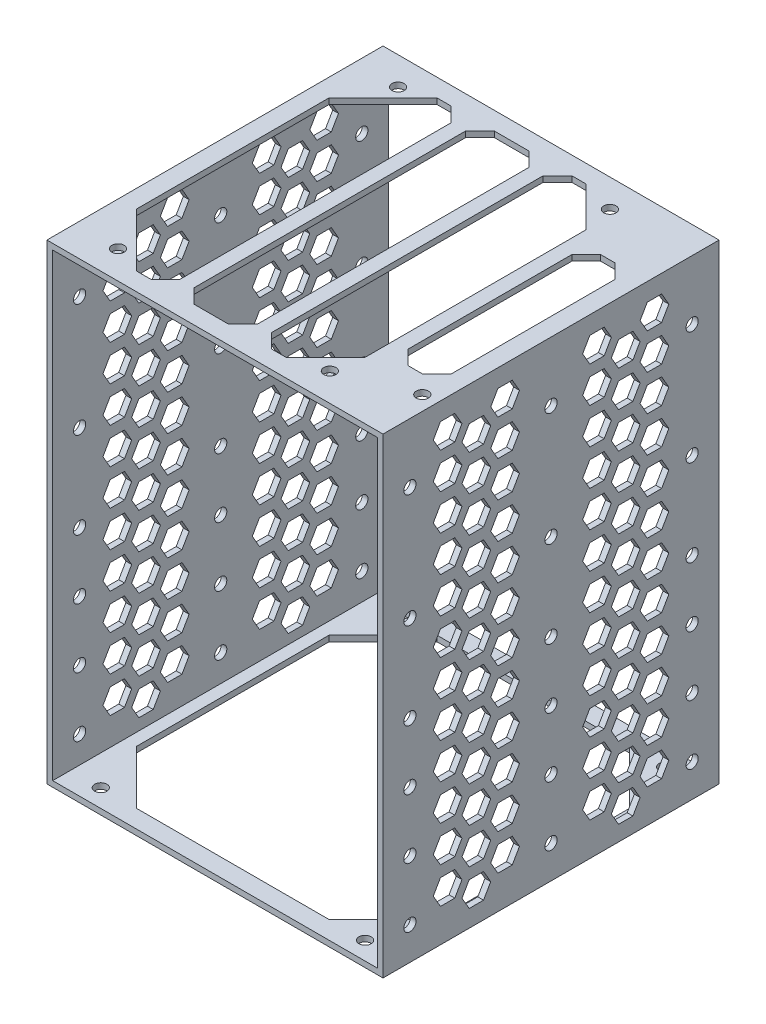
SolidWorks part; units mm, degrees
ref_plane "Front Plane" through (0, 0, 0) normal (0, 0, 1) x (1, 0, 0)
ref_plane "Top Plane" through (0, 0, 0) normal (0, 1, 0) x (1, 0, 0)
ref_plane "Right Plane" through (0, 0, 0) normal (1, 0, 0) x (0, 0, -1)
sketch "Sketch1" plane through (0, 0, 0) normal (0, 0, 1) x (1, 0, 0)
  line L0 (-45.2, 26.84) -> (45.2, 26.84)
  line L1 (45.2, 26.84) -> (45.2, -101.16)
  line L2 (45.2, -101.16) -> (-45.2, -101.16)
  line L3 (-45.2, -101.16) -> (-45.2, 26.84)
  line L5 (-46.8, 28.44) -> (46.8, 28.44)
  line L6 (-46.8, 28.44) -> (-46.8, -102.76)
  line L7 (-46.8, -102.76) -> (46.8, -102.76)
  line L8 (46.8, 28.44) -> (46.8, -102.76)
  dimension "D1" = 90.4
  dimension "D2" = 128
  dimension "D3" = 1.6
  dimension "D4" = 1.6
  dimension "D5" = 1.6
  dimension "D6" = 1.6
  dimension "D7" = 45.2
  dimension "D8" = 45.2
extrude "Boss-Extrude1" add sketch "Sketch1" along normal blind 93.6
sketch "Sketch2" plane through (46.8, 0, 0) normal (1, 0, 0) x (0, 0, -1)
  line L0 (-93.6, 28.44) -> (-93.6, -102.76)
  line L1 (-93.6, 28.44) -> (0, 28.44) construction
  line L2 (-93.6, -102.76) -> (-93.6, 28.44) construction
  line L3 (-93.6, -102.76) -> (0, -102.76) construction
  line L4 (-93.6, -85.36) -> (0, -85.36) construction
  line L5 (0, -102.76) -> (0, 28.44) construction
  line L6 (-93.6, -68.76) -> (0, -68.76) construction
  line L7 (-93.6, -52.16) -> (0, -52.16) construction
  line L8 (-93.6, -35.56) -> (0, -35.56) construction
  line L9 (-93.6, -3.96) -> (0, -3.96) construction
  line L10 (-93.6, -43.86) -> (0, -43.86)
  line L11 (-93.6, -60.46) -> (0, -60.46)
  line L12 (-93.6, -77.06) -> (0, -77.06)
  line L13 (-93.6, -93.66) -> (0, -93.66)
  line L14 (-93.6, -19.76) -> (0, -19.76)
  line L15 (-93.6, 11.84) -> (0, 11.84)
  line L16 (-93.6, -12.26) -> (0, -12.26)
  line L17 (-93.6, -84.56) -> (0, -84.56)
  line L18 (0, -84.56) -> (0, -86.16)
  line L19 (0, -86.16) -> (-93.6, -86.16)
  line L20 (-93.6, -67.96) -> (0, -67.96)
  line L21 (0, -67.96) -> (0, -69.56)
  line L22 (0, -69.56) -> (-93.6, -69.56)
  line L23 (-93.6, -51.36) -> (0, -51.36)
  line L24 (0, -51.36) -> (0, -52.96)
  line L25 (0, -52.96) -> (-93.6, -52.96)
  line L26 (-93.6, -34.76) -> (0, -34.76)
  line L27 (-93.6, -36.36) -> (0, -36.36)
  line L29 (-93.6, -3.16) -> (0, -3.16)
  line L30 (0, -3.16) -> (0, -4.76)
  line L31 (0, -4.76) -> (-93.6, -4.76)
  circle A11 centre (-86.1, 11.84) radius 0.75
  circle A13 centre (-86.1, -19.76) radius 0.75
  circle A14 centre (-86.1, -43.86) radius 0.75
  circle A15 centre (-86.1, -60.46) radius 0.75
  circle A16 centre (-86.1, -77.06) radius 0.75
  circle A17 centre (-86.1, -93.66) radius 0.75
  circle A18 centre (-7.5, 11.84) radius 0.75
  circle A20 centre (-7.5, -19.76) radius 0.75
  circle A21 centre (-7.5, -43.86) radius 0.75
  circle A22 centre (-7.5, -60.46) radius 0.75
  circle A23 centre (-7.5, -77.06) radius 0.75
  circle A24 centre (-7.5, -93.66) radius 0.75
  circle A27 centre (-46.8, 11.84) radius 0.75
  circle A29 centre (-46.8, -19.76) radius 0.75
  circle A30 centre (-46.8, -43.86) radius 0.75
  circle A31 centre (-46.8, -60.46) radius 0.75
  circle A32 centre (-46.8, -77.06) radius 0.75
  circle A33 centre (-46.8, -93.66) radius 0.75
  dimension "D7" = 16.6
  dimension "D8" = 15.8
  dimension "D9" = 8.3
  dimension "D10" = 8.3
  dimension "D11" = 8.3
  dimension "D12" = 8.3
  dimension "D13" = 1.5
  dimension "D14" = 7.5
  dimension "D15" = 7.5
  dimension "D16" = 1.5
  dimension "D17" = 1.5
  dimension "D18" = 1.5
  dimension "D19" = 1.5
  dimension "D20" = 1.5
  dimension "D21" = 1.5
  dimension "D22" = 1.5
  dimension "D23" = 1.5
  dimension "D24" = 1.5
  dimension "D25" = 1.5
  dimension "D26" = 1.5
  dimension "D39" = 1.5
  dimension "D1" = 17.4
  dimension "D2" = 16.6
  dimension "D3" = 16.6
  dimension "D4" = 16.6
  dimension "D5" = 31.6
  dimension "D6" = 32.4
  dimension "D27" = 8.3
  dimension "D28" = 0.8
  dimension "D29" = 0.8
  dimension "D30" = 0.8
  dimension "D31" = 0.8
  dimension "D32" = 0.8
  dimension "D33" = 0.8
  dimension "D34" = 0.8
  dimension "D35" = 0.8
  dimension "D36" = 0.8
  dimension "D37" = 0.8
  dimension "D38" = 15
extrude "Cut-Extrude1" cut sketch "Sketch2" against normal blind 100 contours L15 A11 | L15 A11 | L15 A18 | L15 A18 | L14 A13 | L14 A13 | L10 A21 | L10 A14 | L11 A15 | L11 A22 | L11 A22 | L12 A16 | L12 A16 | L12 A23 | L13 A17 | L13 A17 | L12 A23 | L13 A24 | L13 A24 | A20 | A21 | A14 | A15 | A27 | A29 | A30 | A31 | A32 | A33 region at (46.8, -19.4417, 86.1) region at (46.8, -20.0783, 86.1) region at (46.8, -44.1783, 7.5) region at (46.8, -43.5417, 86.1) region at (46.8, -60.1417, 7.5) region at (46.8, -60.7783, 7.5) region at (46.8, -60.1417, 86.1) region at (46.8, -76.7417, 7.5) region at (46.8, -77.3783, 7.5) region at (46.8, -76.7417, 86.1) region at (46.8, -77.3783, 86.1) region at (46.8, -93.3417, 7.5) region at (46.8, -93.9783, 7.5) region at (46.8, -93.3417, 86.1) region at (46.8, -93.9783, 86.1) region at (46.8, 12.1583, 7.5) region at (46.8, 11.5217, 7.5) region at (46.8, 12.1583, 86.1) region at (46.8, 11.5217, 86.1)
sketch "Sketch6" plane through (46.8, 0, 0) normal (1, 0, 0) x (0, 0, -1)
  line L18 (-93.6, 28.44) -> (0, 28.44) construction
  line L26 (-79.6, 19.9759) -> (-77.6, 23.44)
  line L27 (-77.6, 23.44) -> (-73.6, 23.44)
  line L28 (-73.6, 23.44) -> (-71.6, 19.9759)
  line L29 (-71.6, 19.9759) -> (-73.6, 16.5118)
  line L30 (-73.6, 16.5118) -> (-77.6, 16.5118)
  line L31 (-77.6, 16.5118) -> (-79.6, 19.9759)
  line L32 (-71.6, 15.4759) -> (-69.6, 18.94)
  line L33 (-69.6, 18.94) -> (-65.6, 18.94)
  line L34 (-65.6, 18.94) -> (-63.6, 15.4759)
  line L35 (-63.6, 15.4759) -> (-65.6, 12.0118)
  line L36 (-65.6, 12.0118) -> (-69.6, 12.0118)
  line L37 (-69.6, 12.0118) -> (-71.6, 15.4759)
  line L38 (-63.6, 19.9759) -> (-61.6, 23.44)
  line L39 (-61.6, 23.44) -> (-57.6, 23.44)
  line L40 (-57.6, 23.44) -> (-55.6, 19.9759)
  line L41 (-55.6, 19.9759) -> (-57.6, 16.5118)
  line L42 (-57.6, 16.5118) -> (-61.6, 16.5118)
  line L43 (-61.6, 16.5118) -> (-63.6, 19.9759)
  line L44 (-38, 19.9759) -> (-36, 23.44)
  line L45 (-36, 23.44) -> (-32, 23.44)
  line L46 (-32, 23.44) -> (-30, 19.9759)
  line L47 (-30, 19.9759) -> (-32, 16.5118)
  line L48 (-32, 16.5118) -> (-36, 16.5118)
  line L49 (-36, 16.5118) -> (-38, 19.9759)
  line L50 (-30, 14.9759) -> (-28, 18.44)
  line L51 (-28, 18.44) -> (-24, 18.44)
  line L52 (-24, 18.44) -> (-22, 14.9759)
  line L53 (-22, 14.9759) -> (-24, 11.5118)
  line L54 (-24, 11.5118) -> (-28, 11.5118)
  line L55 (-28, 11.5118) -> (-30, 14.9759)
  line L56 (-22, 19.9759) -> (-20, 23.44)
  line L57 (-20, 23.44) -> (-16, 23.44)
  line L58 (-16, 23.44) -> (-14, 19.9759)
  line L59 (-14, 19.9759) -> (-16, 16.5118)
  line L60 (-16, 16.5118) -> (-20, 16.5118)
  line L61 (-20, 16.5118) -> (-22, 19.9759)
  circle A0 centre (-86.1, 11.84) radius 0.75 construction
  circle A1 centre (-7.5, 11.84) radius 0.75 construction
  dimension "D1" = 120
  dimension "D2" = 120
  dimension "D3" = 120
  dimension "D4" = 4
  dimension "D5" = 4
  dimension "D6" = 4
  dimension "D7" = 120
  dimension "D8" = 120
  dimension "D9" = 120
  dimension "D10" = 4
  dimension "D11" = 4
  dimension "D12" = 4
  dimension "D13" = 2.25
  dimension "D14" = 120
  dimension "D15" = 120
  dimension "D16" = 120
  dimension "D17" = 4
  dimension "D18" = 4
  dimension "D19" = 4
  dimension "D20" = 4
  dimension "D21" = 4
  dimension "D22" = 4
  dimension "D23" = 120
  dimension "D24" = 120
  dimension "D25" = 120
  dimension "D26" = 4
  dimension "D27" = 4
  dimension "D28" = 4
  dimension "D29" = 120
  dimension "D30" = 120
  dimension "D31" = 6.5
  dimension "D32" = 4
  dimension "D33" = 5
  dimension "D34" = 5
  dimension "D35" = 4
  dimension "D36" = 4
  dimension "D37" = 5
  dimension "D38" = 10
  dimension "D39" = 5
  dimension "D40" = 4
  dimension "D41" = 4
  dimension "D42" = 6.5
  dimension "D43" = 4
extrude "Cut-Extrude4" cut sketch "Sketch6" against normal blind 100
hole_wizard "M3 Clearance Hole1" positions "Sketch7" profile "Sketch8" hole size "M3" standard "ANSI Metric" end condition through all
sketch "Sketch7" plane through (-46.8, 0, 0) normal (-1, 0, 0) x (0, 0, 1)
  point P0 (7.5, 11.84)
  point P3 (86.1, 11.84)
  point P6 (7.5, -19.76)
  point P9 (7.5, -43.86)
  point P12 (86.1, -19.76)
  point P15 (86.1, -43.86)
  point P18 (86.1, -60.46)
  point P21 (86.1, -77.06)
  point P26 (7.5, -93.66)
  point P29 (7.5, -77.06)
  point P32 (7.5, -60.46)
  point P40 (86.1, -93.66)
  point P46 (46.8, -77.06)
  point P49 (46.8, -93.66)
  point P52 (46.8, -60.46)
  point P55 (46.8, -43.86)
  point P58 (46.8, -19.76)
  point P61 (46.8, 11.84)
sketch "Sketch8" plane through (-46.8, 11.84, 7.5) normal (0, 1, 0) x (0, 0, 1)
  line L0 (0, 0) -> (0, 93.6)
  line L1 (0, 93.6) -> (1.7, 93.6)
  line L2 (1.7, 93.6) -> (1.7, 0)
  line L5 (1.7, 0) -> (0, 0)
  line L11 (0, -6.35) -> (0, 107.95) construction
  dimension "Thru Hole Dia." = 3.4
  dimension "Thru Hole Depth" = 93.6
sketch "Sketch9" plane through (0, 0, 0) normal (0, 0, 1) x (1, 0, 0)
  line L1 (-30, -108.3026) -> (30, -108.3026)
  line L2 (-30, -108.3026) -> (-30, -39.5314)
  line L3 (-30, -39.5314) -> (30, -39.5314)
  line L4 (30, -108.3026) -> (30, -39.5314)
  dimension "D1" = 30
  dimension "D2" = 30
sketch "Sketch10" plane through (0, -102.76, 0) normal (0, -1, 0) x (1, 0, 0)
  line L0 (45.2, 93.6) -> (-45.2, 93.6) construction
  line L3 (-46.8, 0) -> (46.8, 0) construction
  line L5 (-46.8, 0) -> (46.8, 0) construction
  line L6 (-46.8, 93.6) -> (46.8, 93.6) construction
  line L7 (-46.8, 93.6) -> (-46.8, 0) construction
  line L8 (46.8, 93.6) -> (46.8, 0) construction
  circle A0 centre (-36.8, 88.6) radius 2.9453
  circle A1 centre (-36.8, 5) radius 1.9301
  circle A2 centre (36.8, 5) radius 1.9498
  circle A3 centre (36.8, 88.6) radius 2.427
  dimension "D1" = 5
  dimension "D2" = 10
  dimension "D3" = 10
  dimension "D4" = 5
  dimension "D5" = 10
  dimension "D6" = 5
  dimension "D7" = 5
  dimension "D8" = 10
hole_wizard "M3 Clearance Hole2" positions "Sketch11" profile "Sketch12" hole size "M3" standard "ANSI Metric" end condition up to next
sketch "Sketch11" plane through (0, -102.76, 0) normal (0, -1, 0) x (-1, 0, 0)
  point P0 (-36.8, -5)
  point P3 (-36.8, -88.6)
  point P6 (36.8, -88.6)
  point P9 (36.8, -5)
sketch "Sketch12" plane through (36.8, -102.76, 5) normal (1, 0, 0) x (0, 0, -1)
  line L0 (0, 0) -> (0, 1.6)
  line L1 (0, 1.6) -> (1.7, 1.6)
  line L2 (1.7, 1.6) -> (1.7, 0)
  line L5 (1.7, 0) -> (0, 0)
  line L11 (0, -6.35) -> (0, 107.95) construction
  dimension "Thru Hole Dia." = 3.4
  dimension "Thru Hole Depth" = 1.6
pattern_linear "LPattern1" count 12 spacing 10 along (0, -1, 0) of "Cut-Extrude4"
sketch "Sketch16" plane through (0, 28.44, 0) normal (0, 1, 0) x (1, 0, 0)
  line L0 (46.8, -93.6) -> (46.8, 0) construction
  line L1 (46.8, -93.6) -> (-46.8, -93.6) construction
  circle A0 centre (42.75, -78.6) radius 1.7
  dimension "D1" = 3.4
  dimension "D2" = 4.05
  dimension "D3" = 15
extrude "Cut-Extrude6" cut sketch "Sketch16" against normal blind 141
hole_wizard "M3 Clearance Hole3" positions "Sketch17" profile "Sketch18" hole size "M3" standard "ANSI Metric" end condition up to next
sketch "Sketch17" plane through (0, 28.44, 0) normal (0, 1, 0) x (1, 0, 0)
  line L0 (-46.8, -93.6) -> (-46.8, 0) construction
  line L2 (46.8, 0) -> (-46.8, 0) construction
  circle A0 centre (42.75, -78.6) radius 1.7 construction
  point P0 (-34.8, -7.8)
  point P2 (-34.8, -85.8)
  point P4 (24.2, -85.8)
  point P6 (24.2, -7.8)
  dimension "D1" = 12
  dimension "D2" = 7.8
  dimension "D3" = 59
  dimension "D4" = 78
  dimension "D5" = 18.55
sketch "Sketch18" plane through (-34.8, 28.44, 7.8) normal (1, 0, 0) x (0, 0, 1)
  line L0 (0, 0) -> (0, 1.6)
  line L1 (0, 1.6) -> (1.7, 1.6)
  line L2 (1.7, 1.6) -> (1.7, 0)
  line L5 (1.7, 0) -> (0, 0)
  line L11 (0, -6.35) -> (0, 107.95) construction
  dimension "Thru Hole Dia." = 3.4
  dimension "Thru Hole Depth" = 1.6
sketch "Sketch19" plane through (0, 28.44, 0) normal (0, 1, 0) x (1, 0, 0)
  line L15 (-26.8, -5) -> (-41.8, -20)
  line L16 (-41.8, -73.6) -> (-26.8, -88.6)
  line L17 (41.8, -73.6) -> (29.8, -73.6)
  line L18 (29.8, -73.6) -> (14.8, -88.6)
  line L19 (41.8, -88.6) -> (41.8, -5)
  line L20 (-41.8, -88.6) -> (41.8, -88.6)
  line L21 (-41.8, -5) -> (-41.8, -88.6)
  line L22 (41.8, -5) -> (-41.8, -5)
  line L23 (41.8, -88.6) -> (41.8, -5)
  line L24 (-26.8, -88.6) -> (41.8, -88.6)
  line L25 (-41.8, -20) -> (-41.8, -73.6)
  line L26 (41.8, -5) -> (-26.8, -5)
  line L27 (41.8, -20) -> (29.8, -20)
  line L28 (29.8, -20) -> (14.8, -5)
  line L29 (-18.8, -5) -> (-18.8, -88.6)
  line L30 (-14.8, -88.6) -> (-14.8, -5)
  line L31 (6.8, -5) -> (6.8, -88.6)
  line L32 (2.8, -5) -> (2.8, -88.6)
  line L33 (29.8, -73.6) -> (29.8, -20)
  line L34 (25.8, -77.6) -> (25.8, -16)
  dimension "D1" = 5
  dimension "D2" = 12
  dimension "D3" = 4
  dimension "D6" = 4
  dimension "D7" = 8
  dimension "D8" = 8
  dimension "D9" = 4
extrude "Cut-Extrude7" cut sketch "Sketch19" against normal blind 1.6 contours L29 L26 L15 L25 L16 L24 | L32 L26 L30 L24 | L18 L34 L28 L26 L31 L24 | L33 L17 L23 L27 region at (-29.4386, 28.44, 46.8) region at (-6, 28.44, 46.8) region at (15.819, 28.44, 46.8) region at (35.8, 28.44, 46.8)
chamfer "Chamfer1" distance 4 angle 45 12 edges at (-18.8, 27.64, 88.6) (2.8, 27.64, 88.6) (-14.8, 27.64, 88.6) (6.8, 27.64, 88.6) (6.8, 27.64, 5) (-14.8, 27.64, 5) (-18.8, 27.64, 5) (2.8, 27.64, 5) (41.8, 27.64, 73.6) (41.8, 27.64, 20) (29.8, 27.64, 20) (29.8, 27.64, 73.6)
sketch "Sketch20" plane through (0, -102.76, 0) normal (0, -1, 0) x (1, 0, 0)
  line L10 (-41.8, 20) -> (-26.8, 5)
  line L11 (26.8, 5) -> (41.8, 20)
  line L12 (41.8, 73.6) -> (26.8, 88.6)
  line L13 (-26.8, 88.6) -> (-41.8, 73.6)
  line L14 (41.8, 5) -> (41.8, 88.6)
  line L15 (-41.8, 5) -> (41.8, 5)
  line L16 (-41.8, 88.6) -> (-41.8, 5)
  line L17 (41.8, 88.6) -> (-41.8, 88.6)
  line L18 (41.8, 20) -> (41.8, 73.6)
  line L19 (-26.8, 5) -> (26.8, 5)
  line L20 (-41.8, 73.6) -> (-41.8, 20)
  line L21 (26.8, 88.6) -> (-26.8, 88.6)
  dimension "D1" = 5
extrude "Cut-Extrude8" cut sketch "Sketch20" against normal blind 10
